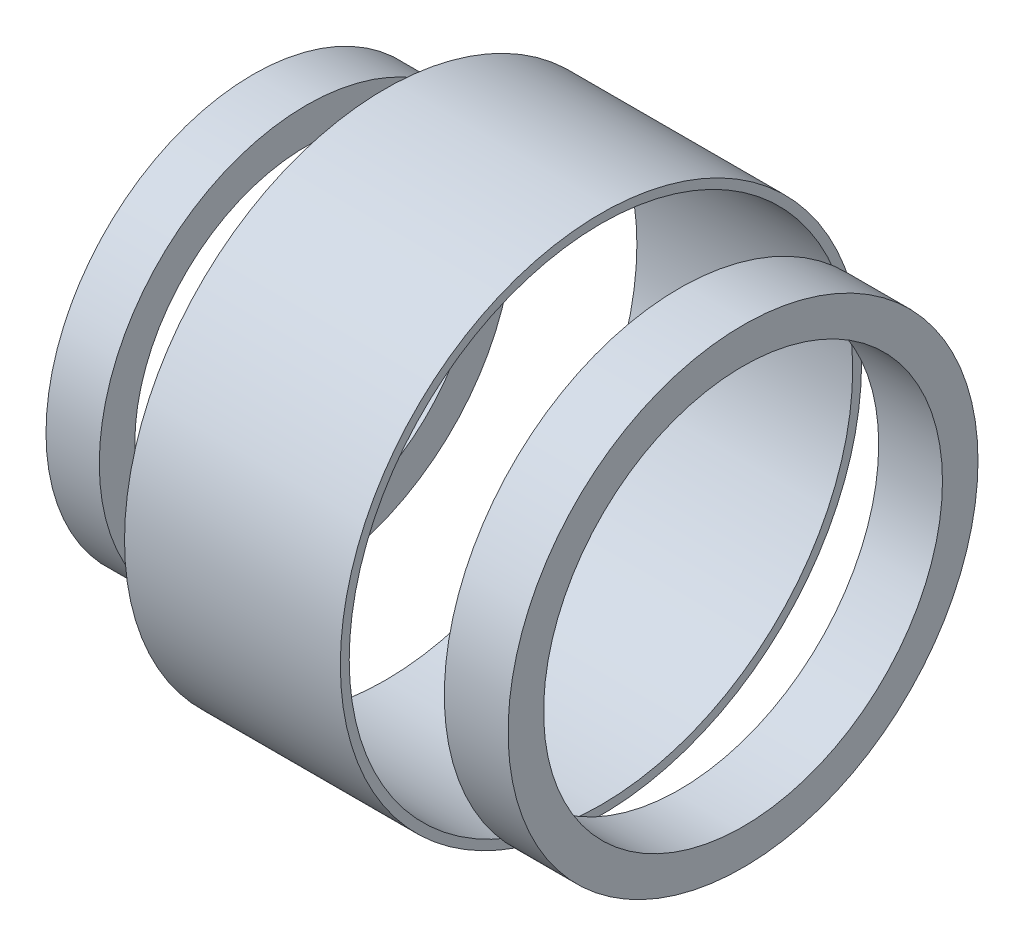
SolidWorks part; units mm, degrees
ref_plane "Front Plane" through (0, 0, 0) normal (0, 0, 1) x (1, 0, 0)
ref_plane "Top Plane" through (0, 0, 0) normal (0, 1, 0) x (1, 0, 0)
ref_plane "Right Plane" through (0, 0, 0) normal (1, 0, 0) x (0, 0, -1)
sketch "Sketch1" plane through (0, 0, 0) normal (0, 0, 1) x (1, 0, 0)
  line L0 (-80.6125, 15) -> (-73.6125, 15)
  line L1 (-73.6125, -15) -> (-80.6125, -15)
  line L2 (-73.6125, -15) -> (-80.6125, -15)
  line L3 (-80.6125, 15) -> (-73.6125, 15)
  line L4 (-67.9125, 15) -> (-60.9125, 15)
  line L5 (-60.9125, -15) -> (-67.9125, -15)
  line L6 (-60.9125, -15) -> (-67.9125, -15)
  line L7 (-67.9125, 15) -> (-60.9125, 15)
  line L8 (-106.95, 12.5) -> (-99.95, 12.5)
  line L9 (-99.95, -12.5) -> (-106.95, -12.5)
  line L10 (-99.95, -12.5) -> (-106.95, -12.5)
  line L11 (-106.95, 12.5) -> (-99.95, 12.5)
  line L12 (-118.7125, 12.5) -> (-111.7125, 12.5)
  line L13 (-111.7125, -12.5) -> (-118.7125, -12.5)
  line L14 (-111.7125, -12.5) -> (-118.7125, -12.5)
  line L15 (-118.7125, 12.5) -> (-111.7125, 12.5)
  line L16 (-80.6125, -21) -> (-57.1188, -21)
  line L17 (-57.1188, 21) -> (-80.6125, 21)
  line L18 (-57.1188, 21) -> (-80.6125, 21)
  line L19 (-80.6125, -21) -> (-57.1188, -21)
  line L20 (-122.5063, -18.5) -> (-99.95, -18.5)
  line L21 (-99.95, 18.5) -> (-122.5063, 18.5)
  line L22 (-99.95, 18.5) -> (-122.5063, 18.5)
  line L23 (-122.5063, -18.5) -> (-99.95, -18.5)
  line L24 (25.7162, 0) -> (-134.3819, 0) construction
  line L26 (-67.9125, 21) -> (-73.6125, 21)
  line L27 (-67.9125, 21) -> (-67.9125, 17.825)
  line L28 (-67.9125, 17.825) -> (-73.6125, 17.825)
  line L29 (-73.6125, 21) -> (-73.6125, 17.825)
  line L30 (-106.95, 18.5) -> (-111.7125, 18.5)
  line L31 (-106.95, 18.5) -> (-106.95, 15.325)
  line L32 (-106.95, 15.325) -> (-111.7125, 15.325)
  line L33 (-111.7125, 18.5) -> (-111.7125, 15.325)
  dimension "D1" = 3.175
revolve "Revolve1" add sketch "Sketch1" angle 360 about L24 region at (-70.7625, 19.4125, 0) region at (-109.3313, 16.9125, 0)
ref_axis "Axis1" through (-121.0609, 0, 0) along (1, 0, 0)
sketch "Sketch2" plane through (0, 0, 0) normal (0, 1, 0) x (1, 0, 0)
  line L0 (-99.9, 29) -> (-99.9, -29) construction
  line L1 (-80.6125, 23.2938) -> (-99.9, 23.2938)
  line L2 (-80.6125, 23.2938) -> (-80.6125, 22.5)
  line L3 (-80.6125, 22.5) -> (-99.9, 22.5)
  line L4 (-99.9, 23.2938) -> (-99.9, 22.5)
  dimension "D1" = 0.7937
revolve "Revolve2" add sketch "Sketch2" angle 360 about axis through (-121.0609, 0, 0) along (1, 0, 0)
